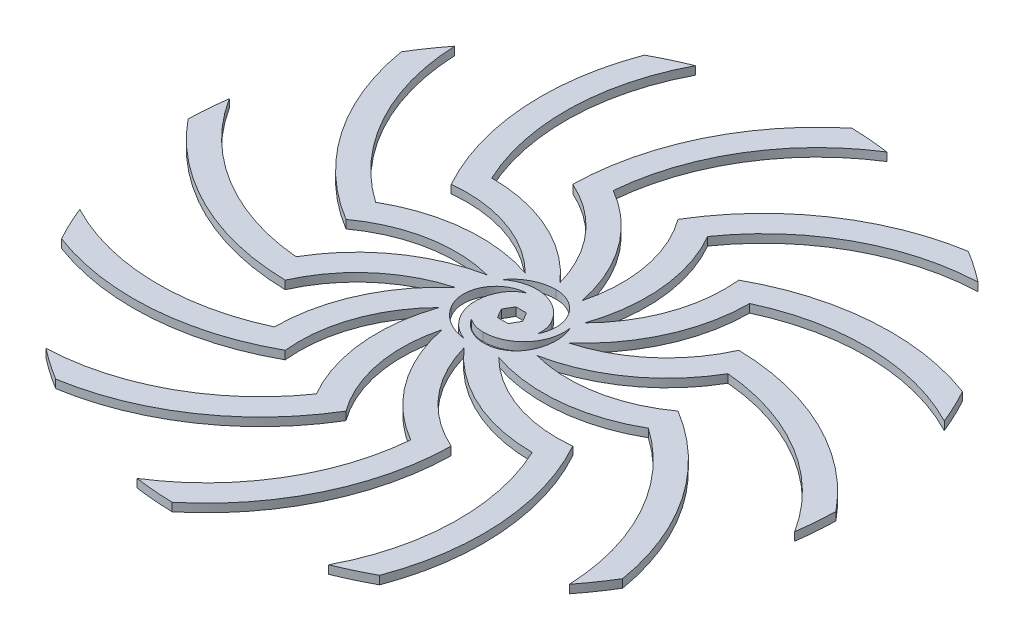
SolidWorks part; units mm, degrees
ref_plane "Front Plane" through (0, 0, 0) normal (0, 0, 1) x (1, 0, 0)
ref_plane "Top Plane" through (0, 0, 0) normal (0, 1, 0) x (1, 0, 0)
ref_plane "Right Plane" through (0, 0, 0) normal (1, 0, 0) x (0, 0, -1)
sketch "Sketch1" plane through (0, 0, 0) normal (0, 1, 0) x (1, 0, 0)
  line L0 (0, 0) -> (3.5728, 0)
  line L1 (0, 0) -> (0, 40) construction
  circle A0 centre (0, 0) radius 40
  circle A1 centre (0, 0) radius 42
  arc A2 (0, 0) -> (0, 20) centre (-13.7477, 10) ccw
  arc A3 (3.5728, 0) -> (3.5728, 20) centre (-13.7477, 10) ccw
  arc A4 (0, 20) -> (20.8254, 34.1512) centre (25.7173, 4.5527) cw
  arc A5 (3.5728, 20) -> (24.614, 31.5301) centre (25.7173, 4.5527) cw
  point P13 (0, 20)
  dimension "D1" = 80
  dimension "D2" = 84
  dimension "D3" = 17
  dimension "D4" = 20
  dimension "D5" = 30
  dimension "D6" = 27
extrude "Boss-Extrude1" add sketch "Sketch1" along normal blind 1 contours A3 A5 A0 A4 A2 L0 region at (3.6732, 0, -10)
ref_axis "Axis1" through (0, 0, 0) along (0, 1, 0)
pattern_circular "CirPattern1" count 12 over 360 about axis through (0, 0, 0) along (0, 1, 0) of bodies 101
sketch "Sketch2" plane through (0, 0, 0) normal (0, 1, 0) x (1, 0, 0)
  arc A0 (0, 0) -> (20, 0) centre (10, 13.7477) ccw construction
  arc A1 (1.7864, -3.0941) -> (19.1069, 6.9059) centre (1.7864, 16.9059) ccw construction
  arc A2 (0, 0) -> (20, 0) centre (10, 13.7477) ccw
  arc A3 (1.7864, -3.0941) -> (19.1069, 6.9059) centre (1.7864, 16.9059) ccw
  circle A4 centre (0, 0) radius 6.3246
  point P7 (5.7174, -2.704)
extrude "Boss-Extrude2" add sketch "Sketch2" along normal up to surface (1 mm away) contours A4 region at (5.9964, 0, 1.3465) up to face at (-20.5854, 1, 1.1757)
sketch "Sketch3" plane through (0, 1, 0) normal (0, 1, 0) x (1, 0, 0)
  line L0 (0, 0) -> (0, 1.4123) construction
  arc A0 (-2.1651, 1.25) -> (4.6112, -2.6623) centre (1.2231, -0.7061) ccw
  circle A1 centre (0, 0) radius 6.3246
  circle A2 centre (0, 0) radius 6.3246
  arc A3 (-3.0311, 1.75) -> (-0.5188, -5.2992) centre (1.2231, -0.7061) ccw
  circle A4 centre (0, 0) radius 5.3246
  circle A5 centre (0, 0) radius 2.5
  arc A6 (0, -2.5) -> (0, 5.3246) centre (0, 1.4123) ccw
  circle A7 centre (0, 0) radius 3.5
  arc A8 (0, -3.5) -> (4.8487, 2.2003) centre (0, 1.4123) ccw
  arc A9 (2.1651, 1.25) -> (-4.6112, -2.6623) centre (-1.2231, -0.7061) ccw
  arc A10 (3.0311, 1.75) -> (-4.3299, 3.0989) centre (-1.2231, -0.7061) ccw
  dimension "D3" = 5
  dimension "D4" = 7
  dimension "D1" = 0
  dimension "D2" = 1
  dimension "D5" = 3
extrude "Cut-Extrude1" cut sketch "Sketch3" against normal through all contours A7 A9 A4 A3 | A10 A7 A6 A4 | A8 A7 A0 A4 region at (2.7046, 1, 2.7563) region at (-3.7394, 1, 0.9641) region at (1.0347, 1, -3.7204)
scale "Scale1" scale about centroid uniform scaling yes scale factor 3.4
sketch "Sketch4" plane through (0, 2.2, 0) normal (0, 1, 0) x (1, 0, 0)
  line L1 (0, 7.3323) -> (-6.35, 3.6662) construction
  line L2 (-6.35, 3.6662) -> (-6.35, -3.6662) construction
  line L3 (-6.35, -3.6662) -> (0, -7.3323) construction
  line L4 (0, -7.3323) -> (6.35, -3.6662) construction
  line L5 (6.35, -3.6662) -> (6.35, 3.6662) construction
  line L6 (6.35, 3.6662) -> (0, 7.3323) construction
  line L7 (2.175, -3.7672) -> (4.35, 0)
  line L8 (4.35, 0) -> (2.175, 3.7672)
  line L9 (2.175, 3.7672) -> (-2.175, 3.7672)
  line L10 (-2.175, 3.7672) -> (-4.35, 0)
  line L11 (-4.35, 0) -> (-2.175, -3.7672)
  line L12 (-2.175, -3.7672) -> (2.175, -3.7672)
  circle A0 centre (0, 0) radius 6.35 construction
  circle A1 centre (0, 0) radius 4.35
  circle A2 centre (0, 0) radius 3.7672 construction
  point P11 (0, 0)
  dimension "D1" = 12.7
  dimension "D2" = 2
extrude "Cut-Extrude2" cut sketch "Sketch4" against normal up to surface (3.4 mm away) contours L11 L12 L7 L8 L9 L10 region at (0, 2.2, 0) up to face at (7.8986, -1.2, 8.4784)
